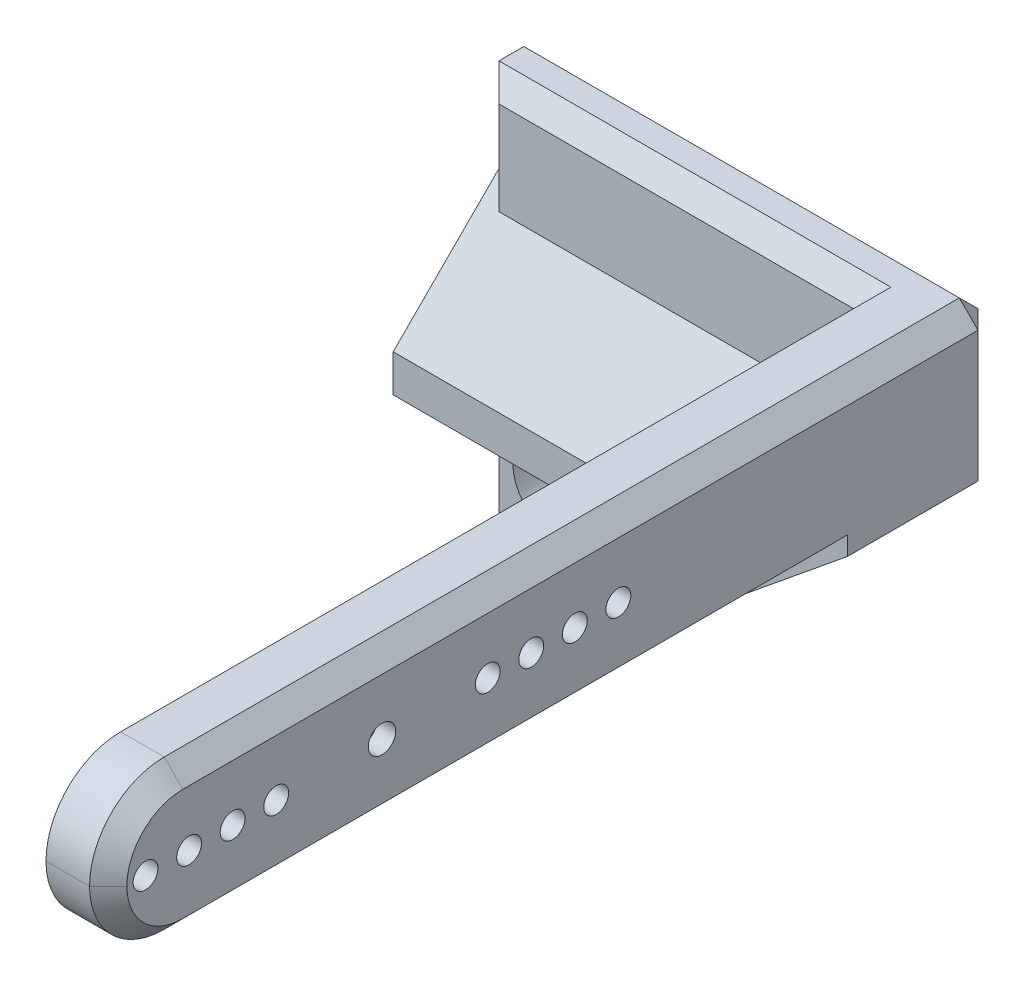
SolidWorks part; units mm, degrees
ref_plane "Alzado" through (0, 0, 0) normal (0, 0, 1) x (1, 0, 0)
ref_plane "Planta" through (0, 0, 0) normal (0, 1, 0) x (1, 0, 0)
ref_plane "Vista lateral" through (0, 0, 0) normal (1, 0, 0) x (0, 0, -1)
sketch "Croquis1" plane through (0, 0, 0) normal (0, 0, 1) x (1, 0, 0)
  line L0 (0, -6) -> (0, -12) construction
  line L1 (-6, 20) -> (25.5, 20)
  line L2 (-6, 20) -> (-6, 0)
  line L3 (-6, 0) -> (6, 0)
  line L4 (25.5, 20) -> (25.5, 8)
  line L5 (0, -6) -> (0, 0) construction
  line L6 (0, -6) -> (0, 0) construction
  line L7 (25.5, 8) -> (6, 8)
  line L8 (6, 8) -> (6, 0)
  line L9 (0, -6) -> (6, -6) construction
  line L10 (-6, 0) -> (6, 0)
  line L11 (-6, 0) -> (-6, -12)
  line L12 (-6, -12) -> (6, -12)
  line L13 (6, 0) -> (6, -12)
  line L14 (0, -6) -> (-6, -6) construction
  circle A0 centre (0, -6) radius 3.375
  dimension "D1" = 6.75
  dimension "D2" = 20
  dimension "D3" = 6
  dimension "D4" = 25.5
  dimension "D5" = 6
  dimension "D7" = 6
  dimension "D8" = 12
extrude "Saliente-Extruir1" add sketch "Croquis1" along normal blind 5 contours A0 L3 L4 L1 L2 | A0 L3 L11 L12 L13
sketch "Croquis2" plane through (25.5, 0, 0) normal (1, 0, 0) x (0, 0, -1)
  line L0 (0, 8) -> (0, -12) construction
  line L1 (0, 8) -> (-71.4, 8)
  line L2 (0, 8) -> (0, 20)
  line L3 (0, 20) -> (-71.4, 20)
  line L4 (-71.4, 8) -> (-71.4, 20)
  line L5 (-49.4, 14) -> (-9.4, 14) construction
  line L6 (0, 8) -> (-9.4, 8)
  line L7 (0, 8) -> (0, 20)
  line L8 (0, 20) -> (-9.4, 20)
  line L9 (-9.4, 8) -> (-9.4, 20) construction
  circle A0 centre (-49.4, 14) radius 2.1
  dimension "D2" = 22
  dimension "D4" = 4.2
  dimension "D1" = 40
  dimension "D3" = 9.4
extrude "Saliente-Extruir2" add sketch "Croquis2" along normal blind 5
sketch "Croquis4" plane through (30.5, 0, 0) normal (1, 0, 0) x (0, 0, -1)
  line L0 (-71.4, 14) -> (0, 14) construction
  line L1 (-57.9, 14) -> (-40.9, 14)
  line L2 (-40.9, 15) -> (-49.4, 15) construction
  line L3 (-68.4, 15) -> (-64.9, 15) construction
  line L4 (-64.9, 15) -> (-61.4, 15) construction
  line L5 (-61.4, 15) -> (-57.9, 15) construction
  line L6 (-57.9, 14) -> (-49.4, 14) construction
  line L7 (-40.9, 15) -> (-37.4, 15) construction
  line L8 (-37.4, 15) -> (-33.9, 15) construction
  line L9 (-33.9, 15) -> (-30.4, 15) construction
  line L10 (-49.4, 15) -> (-57.9, 15) construction
  line L11 (-71.4, 8) -> (-71.4, 20) construction
  line L12 (0, 8) -> (0, 20) construction
  line L13 (-49.4, 15) -> (-49.4, 14) construction
  circle A0 centre (-68.4, 14) radius 1
  circle A1 centre (-64.9, 14) radius 1
  circle A2 centre (-61.4, 14) radius 1
  circle A3 centre (-57.9, 14) radius 1
  circle A4 centre (-40.9, 14) radius 1
  circle A5 centre (-37.4, 14) radius 1
  circle A6 centre (-33.9, 14) radius 1
  circle A7 centre (-30.4, 14) radius 1
  circle A8 centre (-49.4, 14) radius 2.1 construction
  dimension "D1" = 2
  dimension "D3" = 3.5
  dimension "D4" = 8.5
extrude "Cortar-Extruir1" cut sketch "Croquis4" against normal up to next contours A7 | A6 | A5 | A4 | A1 | A0 | A2 | A3
sketch "Croquis5" plane through (30.5, 0, 0) normal (1, 0, 0) x (0, 0, -1)
  circle A0 centre (-57.9, 14) radius 2.1
  circle A1 centre (-64.9, 14) radius 2.1
  circle A2 centre (-40.9, 14) radius 2.1
  circle A3 centre (-33.9, 14) radius 2.1
  dimension "D1" = 4.2
extrude "Cortar-Extruir2" cut sketch "Croquis5" along normal blind 3 from surface at -5 starting at face at (25.5, 14, 29.4)
sketch "Croquis6" plane through (30.5, 0, 0) normal (1, 0, 0) x (0, 0, -1)
  circle A0 centre (-49.4, 14) radius 1.1
  circle A1 centre (-49.4, 14) radius 2.1
  circle A2 centre (-49.4, 14) radius 2.1 construction
  dimension "D1" = 2.2
extrude "Saliente-Extruir4" add sketch "Croquis6" against normal blind 1.5
fillet "Redondeo2" radius 6 4 edges at (25.5, 14, 71.4) (28, 8, 71.4) (30.5, 14, 71.4) (28, 20, 71.4)
sketch "Croquis10" plane through (0, 0, 0) normal (0, 0, -1) x (-1, 0, 0)
  line L0 (-6, 8) -> (-6, -12) construction
  line L1 (-30.5, 8) -> (-6, 8) construction
  line L2 (-6, 8) -> (-6, -12)
  line L3 (-30.5, 8) -> (-6, 8)
  line L4 (-6, -12) -> (-30.5, 8)
extrude "Saliente-Extruir5" add sketch "Croquis10" against normal up to surface (5 mm away) up to face at (8.5, 5.3333, 5)
sketch "Croquis11" plane through (0, 0, 5) normal (0, 0, 1) x (1, 0, 0)
  line L0 (-6, 1) -> (21.925, 1)
  line L1 (-6, 20) -> (-6, -12) construction
  line L2 (30.5, 8) -> (6, -12) construction
  line L3 (-6, 20) -> (25.5, 20) construction
  line L4 (-6, 1) -> (-6, 4)
  line L5 (-16.35, 0.925) -> (16.35, 0.925) construction
  line L6 (-6, 4) -> (20.6, 4)
  line L7 (30.5, 8) -> (21.925, 1)
  line L8 (25.5, 8) -> (20.6, 4)
  line L10 (30.5, 8) -> (25.5, 8)
  dimension "D1" = 0.075
  dimension "D2" = 19
  dimension "D3" = 3
extrude "Saliente-Extruir6" add sketch "Croquis11" along normal blind 7
chamfer "Chaflán1" distance 7 angle 45 1 edges at (7.3, 4, 5)
chamfer "Chaflán2" distance 1.5 angle 45 13 edges at (12.25, 20, 0) (30.5, 9.7574, 69.6426) (30.5, 18.2426, 69.6426) (18.25, -2, 0) (13.9625, -5.5, 5) (-6, -5.5, 5) (9.75, 20, 5) (-6, 15.5, 5) (30.5, 14, 0) (0, -12, 5) (30.5, 20, 32.7) (0, -12, 0) (-6, 4, 0)
